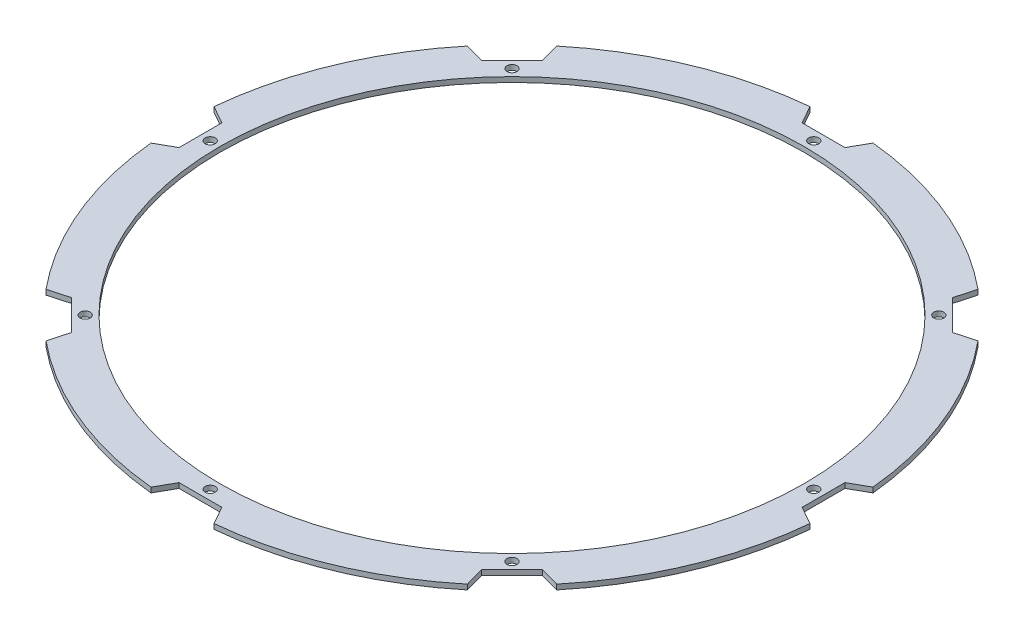
SolidWorks part; units mm, degrees
ref_plane "Front Plane" through (0, 0, 0) normal (0, 0, 1) x (1, 0, 0)
ref_plane "Top Plane" through (0, 0, 0) normal (0, 1, 0) x (1, 0, 0)
ref_plane "Right Plane" through (0, 0, 0) normal (1, 0, 0) x (0, 0, -1)
sketch "Sketch2" plane through (0, 0, 0) normal (0, 1, 0) x (1, 0, 0)
  line L0 (-215.9, 0) -> (-190.5, 0) construction
  line L1 (-190.5, 0) -> (0, 0) construction
  line L2 (0, 0) -> (190.5, 0) construction
  line L3 (190.5, 0) -> (215.9, 0) construction
  line L4 (-214.9183, 20.5652) -> (-203.2, 13.97)
  line L5 (-203.2, 13.97) -> (-203.2, -13.97)
  line L6 (-203.2, -13.97) -> (-214.9175, -20.574)
  circle A0 centre (0, 0) radius 190.5
  circle A1 centre (0, 0) radius 215.9
  circle A2 centre (-196.85, 0) radius 3.302
  point P10 (-203.2, 0)
  point P13 (-203.2, 0)
  point P15 (-190.5, 0)
  dimension "D1" = 381
  dimension "D2" = 431.8
  dimension "D7" = 6.604
  dimension "D3" = 27.94
  dimension "D4" = 6.5952
  dimension "D5" = 6.604
  dimension "D6" = 12.7
  dimension "D8" = 6.35
extrude "Boss-Extrude1" add sketch "Sketch2" along normal blind 3.302 contours L6 A1 L4 L5 A2 A0 region at (10.0035, 0, -209.5617)
pattern_circular "CirPattern1" count 8 over 360 about axis through (0, 3.302, 0) along (0, -1, 0) reverse direction yes of face at (-196.85, 3.302, 3.302) of face at (-203.2, 1.651, 0) of face at (-209.0587, 1.651, 17.272) of face at (-209.0592, 1.651, -17.2676)
sketch "Sketch3" plane through (0, 3.302, 0) normal (0, 1, 0) x (1, 0, 0)
  line L0 (-203.2, 13.97) -> (-203.2, -13.97) construction
  line L1 (0, 0) -> (-190.5, 0) construction
  line L2 (-190.5, 0) -> (-203.2, 0) construction
  line L3 (-203.2, 0) -> (-228.5886, 0) construction
  circle A0 centre (0, 0) radius 190.5 construction
  point P0 (-203.2, 0)
  point P1 (0, 0)
  point P4 (-190.5, 0)
